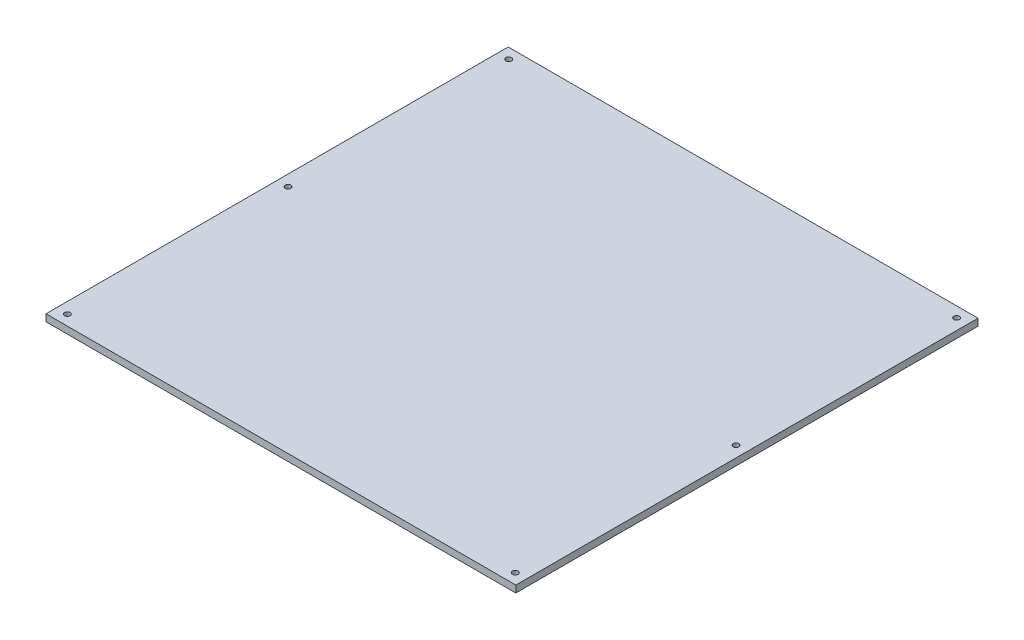
SolidWorks part; units mm, degrees
material "6063-T5"
ref_plane "Front Plane" through (0, 0, 0) normal (0, 0, 1) x (1, 0, 0)
ref_plane "Top Plane" through (0, 0, 0) normal (0, 1, 0) x (1, 0, 0)
ref_plane "Right Plane" through (0, 0, 0) normal (1, 0, 0) x (0, 0, -1)
sketch "Sketch2" plane through (0, 0, 0) normal (0, 1, 0) x (1, 0, 0)
  line L0 (-214.63, -211.1375) -> (214.63, -211.1375)
  line L1 (-214.63, -211.1375) -> (-214.63, 211.1375)
  line L2 (214.63, -211.1375) -> (214.63, 211.1375)
  line L3 (-214.63, 211.1375) -> (214.63, 211.1375)
  line L4 (-214.63, -211.1375) -> (214.63, 211.1375) construction
  line L5 (214.63, -211.1375) -> (-214.63, 211.1375) construction
  line L6 (-204.63, 201.6125) -> (204.63, 201.6125) construction
  line L7 (204.63, 201.6125) -> (204.63, -201.6125) construction
  line L8 (204.63, -201.6125) -> (-204.63, -201.6125) construction
  line L9 (-204.63, -201.6125) -> (-204.63, 201.6125) construction
  line L10 (0, 301.643) -> (0, -298.9072) construction
  line L11 (-264.2047, 0) -> (279.6955, 0) construction
  circle A0 centre (-204.63, 201.6125) radius 2.6
  circle A1 centre (204.63, 201.6125) radius 2.6
  circle A2 centre (204.63, -201.6125) radius 2.6
  circle A3 centre (-204.63, -201.6125) radius 2.6
  circle A4 centre (-204.63, 0) radius 2.6
  circle A5 centre (204.63, 0) radius 2.6
  point P1 (0, 0)
  point P14 (0, 201.6125)
  point P15 (204.63, 0)
  dimension "D3" = 5.2
  dimension "D1" = 429.26
  dimension "D2" = 422.275
  dimension "D4" = 409.26
  dimension "D5" = 403.225
extrude "Boss-Extrude1" add sketch "Sketch2" along normal mid plane 6.35
ref_axis "Axis1" through (-204.63, 3.175, -201.6125) along (0, -1, 0)
ref_axis "Axis3" through (-204.63, 3.175, 201.6125) along (0, -1, 0)
ref_axis "Axis4" through (204.63, 3.175, 0) along (0, -1, 0)
equation "\"D5@Sketch2\"=\"D2@Sketch2\"-.75"
